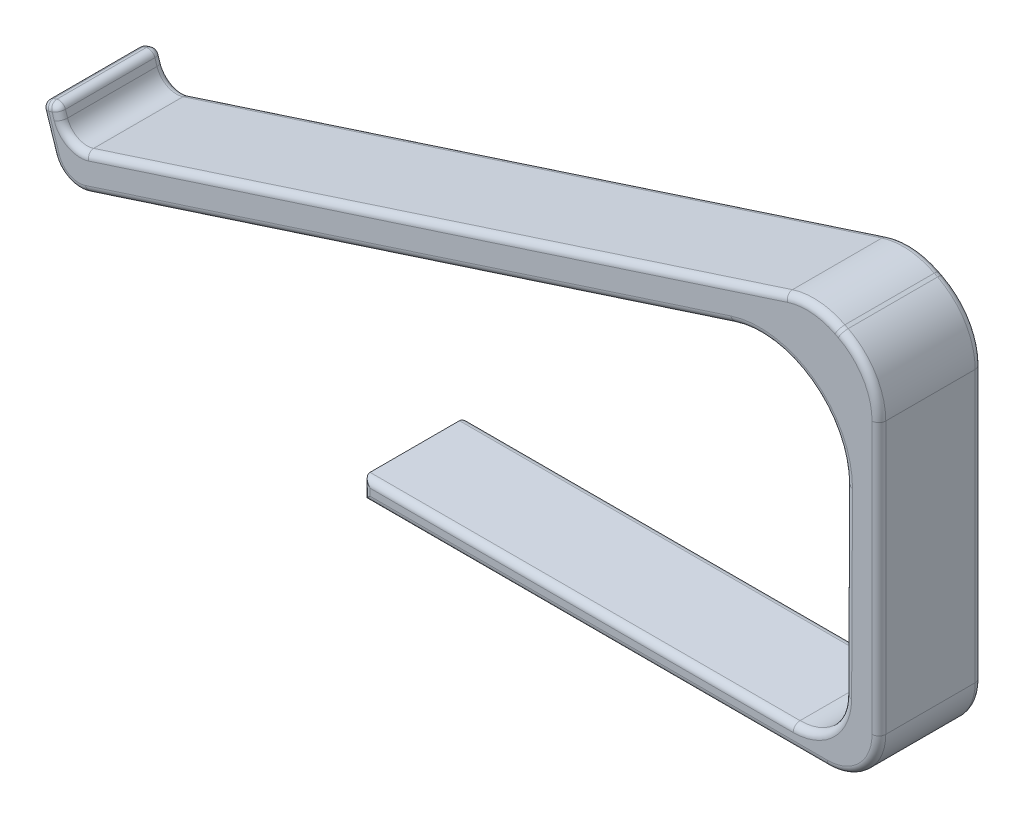
SolidWorks part; units mm, degrees
note: '?' marks a value the reader was unsure of.
ref_plane "Front Plane" through (0, 0, 0) normal (0, 0, 1) x (1, 0, 0)
ref_plane "Top Plane" through (0, 0, 0) normal (0, 1, 0) x (1, 0, 0)
ref_plane "Right Plane" through (0, 0, 0) normal (1, 0, 0) x (0, 0, -1)
ref_axis "Axis1" through (0, 0, -39.8625) along (0, 0, 1)?
ref_axis "Axis2" through (0, -40.0743, 0) along (0, 1, 0)?
ref_axis "Axis3" through (48.4474, 0, 0) along (-1, 0, 0)?
ref_plane "Plane1" through (0, 0, 0) normal (-0.309, 0.9511, 0) x (0, 0, 1)
ref_plane "Plane3" through (0, 44, 0) normal (0, 1, 0) x (1, 0, 0)
sketch "Sketch1" plane through (0, 44, 0) normal (0, 1, 0) x (1, 0, 0)
  line L0 (0, -100) -> (0, 100) construction
  line L1 (0, 100) -> (-110, 100) construction
  line L2 (0, -100) -> (-110, -100) construction
  line L3 (-110, 100) -> (-110, -100) construction
  point P2 (0, 0)
  point P3 (0, 0)
  dimension "D1" = 200
  dimension "D2" = 110
ref_plane "Plane4" through (-23.4353, 72.1266, 0) normal (-0.309, 0.9511, 0) x (0.9511, 0.309, 0)
sketch "Sketch2" plane through (-23.4353, 72.1266, 0) normal (-0.309, 0.9511, 0) x (0.9511, 0.309, 0)
  line L0 (-91.0195, 115) -> (-91.0195, 85)
  line L1 (-91.0195, 115) -> (158.9805, 115)
  line L2 (158.9805, 115) -> (158.9805, 85)
  line L3 (158.9805, 85) -> (-91.0195, 85)
  point P2 (-91.0195, 100)
  dimension "D1" = 30
  dimension "D2" = 250
extrude "Boss-Extrude1" add sketch "Sketch2" against normal blind 10 contours L3 L0 L1 L2
sketch "Sketch3" plane through (-23.4353, 72.1266, 0) normal (-0.309, 0.9511, 0) x (0.9511, 0.309, 0)
  line L0 (-91.0195, 115) -> (-91.0195, 85) construction
  line L1 (-91.0195, 115) -> (-86.0195, 115)
  line L2 (-91.0195, 115) -> (-91.0195, 85)
  line L3 (-91.0195, 85) -> (-86.0195, 85)
  line L4 (-86.0195, 115) -> (-86.0195, 85)
  line L5 (158.9805, 85) -> (-91.0195, 85) construction
  dimension "D1" = 5
extrude "Boss-Extrude2" add sketch "Sketch3" along normal blind 10
sketch "Sketch4" plane through (0, 0, 0) normal (0, 1, 0) x (1, 0, 0)
  line L0 (0, 39.8625) -> (0, -47.0489) construction
  line L1 (130.8543, 115) -> (-19.1457, 115)
  line L2 (130.8543, 115) -> (130.8543, 85)
  line L3 (130.8543, 85) -> (-19.1457, 85)
  line L4 (-19.1457, 115) -> (-19.1457, 85)
  dimension "D1" = 19.1457
  dimension "D2" = 150
  dimension "D3" = 30
extrude "Boss-Extrude3" add sketch "Sketch4" along normal blind 6 separate body
sketch "Sketch5" plane through (0, 6, 0) normal (0, 1, 0) x (1, 0, 0)
  line L0 (-19.1457, 85) -> (130.8543, 85) construction
  line L1 (130.8543, 115) -> (120.8543, 115)
  line L2 (130.8543, 115) -> (130.8543, 85)
  line L3 (130.8543, 85) -> (120.8543, 85)
  line L4 (120.8543, 115) -> (120.8543, 85)
  dimension "D1" = 10
sketch "Sketch6" plane through (-20.3452, 62.616, 0) normal (0.309, -0.9511, 0) x (0.9511, 0.309, 0)
  line L0 (158.9805, -115) -> (158.9805, -85) construction
  line L1 (158.9805, -85) -> (148.9805, -85)
  line L2 (158.9805, -85) -> (158.9805, -115)
  line L3 (158.9805, -115) -> (148.9805, -115)
  line L4 (148.9805, -85) -> (148.9805, -115)
  line L5 (-91.0195, -115) -> (158.9805, -115) construction
  dimension "D1" = 10
loft "Loft1" add profiles "Sketch6", "Sketch5"
fillet "Fillet1" radius 15 2 edges at (130.8543, 0, -100)
fillet "Fillet8" radius 25 1 edges
chamfer "Chamfer1" distance 17 angle 45 1 edges at (127.7641, 121.2542, -100)
fillet "Fillet3" radius 20 2 edges at (130.8543, 106.1885, -100) (111.5962, 116.001, -100)
fillet "Fillet5" radius 6 1 edges at (-105.2447, 45.5451, -100)
fillet "Fillet6" radius 2 36 edges at (2.0895, 80.4201, -115) (-104.1164, 47.7595, -115) (-104.1164, 47.7595, -85) (-107.7169, 53.1535, -85) (-107.7169, 53.1535, -115) (-113.0902, 53.5106, -100) (-110.7125, 54.2831, -85) (-108.3349, 55.0557, -100) (-110.7125, 54.2831, -115) (-19.1457, 3, -115) (48.3543, 0, -85) (-19.1457, 3, -85) (48.3543, 0, -115) (126.4609, 4.3934, -115) (126.4609, 4.3934, -85) (116.5069, 10.3681, -85) (116.5069, 10.3681, -115) (110.9219, 94.3808, -115) (110.9219, 94.3808, -85) (-110, 44, -115) (-110, 44, -85) (119.4558, 111.9963, -85) (2.0895, 80.4201, -85) (111.4669, 114.3582, -85) (127.9071, 104.3824, -85) (119.4558, 111.9963, -115) (111.4669, 114.3582, -115) (127.9071, 104.3824, -115)
fillet "Fillet7" radius 8 3 edges at (-106.5337, 35.2276, -85.5858) (-106.5337, 35.2276, -114.4142) (-106.9098, 34.4894, -100)
sketch "Sketch7" plane through (0, 0, 0) normal (0, -1, 0) x (1, 0, 0)
  line L2 (-25.9564, -115) -> (-25.9564, -85) construction
  line L9 (-25.9564, -112) -> (-1.9564, -112)
  line L10 (-25.9564, -112) -> (-25.9564, -88)
  line L11 (-25.9564, -88) -> (-1.9564, -88)
  line L12 (-1.9564, -112) -> (-1.9564, -88)
  point P6 (-25.9564, -100)
  point P7 (-25.9564, -100)
  dimension "D1" = 30
  dimension "D2" = 24
  dimension "D3" = 24
extrude "Cut-Extrude1" cut sketch "Sketch7" against normal blind 3
